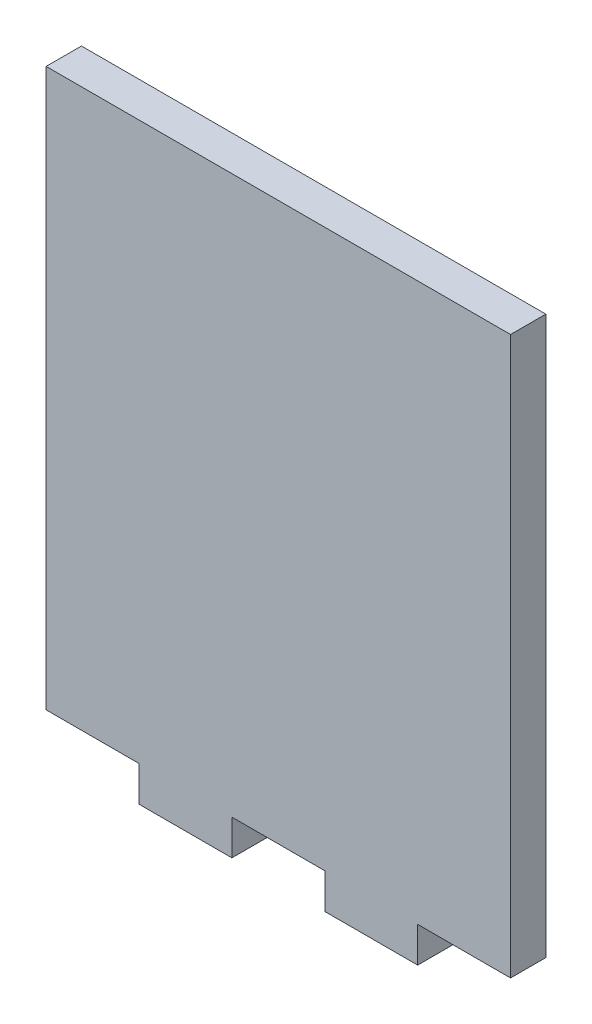
SolidWorks part; units mm, degrees
ref_plane "Front Plane" through (0, 0, 0) normal (0, 0, 1) x (1, 0, 0)
ref_plane "Top Plane" through (0, 0, 0) normal (0, 1, 0) x (1, 0, 0)
ref_plane "Right Plane" through (0, 0, 0) normal (1, 0, 0) x (0, 0, -1)
sketch "Sketch1" plane through (0, 0, 0) normal (0, 0, 1) x (1, 0, 0)
  line L1 (0, 0) -> (63.5, 0)
  line L2 (0, 0) -> (0, 81.026)
  line L3 (0, 81.026) -> (63.5, 81.026)
  line L4 (63.5, 0) -> (63.5, 81.026)
  dimension "D1" = 81.026
  dimension "D2" = 63.5
extrude "Boss-Extrude1" add sketch "Sketch1" along normal blind 4.826
sketch "Sketch2" plane through (0, 0, 4.826) normal (0, 0, 1) x (1, 0, 0)
  line L0 (0, 0) -> (63.5, 0) construction
  line L1 (0, 0) -> (12.7, 0)
  line L2 (0, 0) -> (0, 4.826)
  line L3 (0, 4.826) -> (12.7, 4.826)
  line L4 (12.7, 0) -> (12.7, 4.826)
  line L5 (25.4, 0) -> (38.1, 0)
  line L6 (25.4, 0) -> (25.4, 4.826)
  line L7 (25.4, 4.826) -> (38.1, 4.826)
  line L8 (38.1, 0) -> (38.1, 4.826)
  line L9 (12.7, 4.826) -> (25.4, 4.826) construction
  line L10 (63.5, 0) -> (50.8, 0)
  line L11 (63.5, 0) -> (63.5, 4.826)
  line L12 (63.5, 4.826) -> (50.8, 4.826)
  line L13 (50.8, 0) -> (50.8, 4.826)
  line L14 (38.1, 4.826) -> (50.8, 4.826) construction
  dimension "D1" = 4.826
extrude "Cut-Extrude1" cut sketch "Sketch2" against normal through all
equation "\"MDF\"= 0.19in"
equation "\"PVCID\" = 2.067in"
equation "\"PVCOD\" = 2.375in"
equation "\"GenDiameter\"= 60mm"
equation "\"GenCutDiameter\" = 1.8in"
equation "\"GenCutDistance\" = 1"
equation "\"TowerHeight\" = 6in"
equation "\"TowerFrontBase\" = 3in"
equation "\"FunnelHeight\" = 1in"
equation "\"FunnelAngle\" = 20"
equation "\"TowerSideBase\" = 3in"
equation "\"TowerPanelLength\" = 2in"
equation "\"TowerPanelLeeway\" = 0.5in"
equation "\"BaseLength\" = 9in"
equation "\"BaseWidth\" = 10in"
equation "\"WheelHoleLength\" = 3.25in"
equation "\"WheelHoleWidth\" = 26mm"
equation "\"WheelHoleFromBack\" = 1in"
equation "\"DropLength\" = 1in"
equation "\"DropWidth\" = 8.5in"
equation "\"BumperWidth\" = 1in"
equation "\"SmallHexDiameter\" = 0.185in"
equation "\"SmallHexHeight\" = 0.701in"
equation "\"ScrewSize\" = 0.106in"
equation "\"BigHexDiameter\" = 0.251in"
equation "\"BigHexHeight\" = 0.374in"
equation "\"PCBThickness\" = 0.066in"
equation "\"ConnectorHeight\" = 0.517in"
equation "\"BoardHeight\" = 0.583in"
equation "\"UnoStackHeight\" = 1.351in"
equation "\"UnoStackWidth\" = 3.053in"
equation "\"UnoStackLength\" = 3.152in"
equation "\"HBridgeWidth\" = 1.797in"
equation "\"HBridgeLength\" = 2.236in"
equation "\"DSWidth\" = 1.820in"
equation "\"DSLength\" = 1.833in"
equation "\"StepperWidth\" = 1.799in"
equation "\"StepperLength\" = 2.248in"
equation "\"ULNWidth\" = 1.304in"
equation "\"ULNLength\" = 1.545in"
equation "\"VSwitchHeight\" = 0.392in"
equation "\"VSwitchWidth\" = 0.637in"
equation "\"VSwitchLength\" = 1.097in"
equation "\"SkateWheelDiameter\" = 80mm"
equation "\"SkateWheelThickness\" = 24mm"
equation "\"BaseDistance\" = 3in"
equation "\"DummyVar\" = 2in"
equation "\"D1@Sketch1\"=\"MDF\"+3in"
equation "\"D1@Boss-Extrude1\"=\"MDF\""
equation "\"D1@Sketch2\"=\"MDF\""
